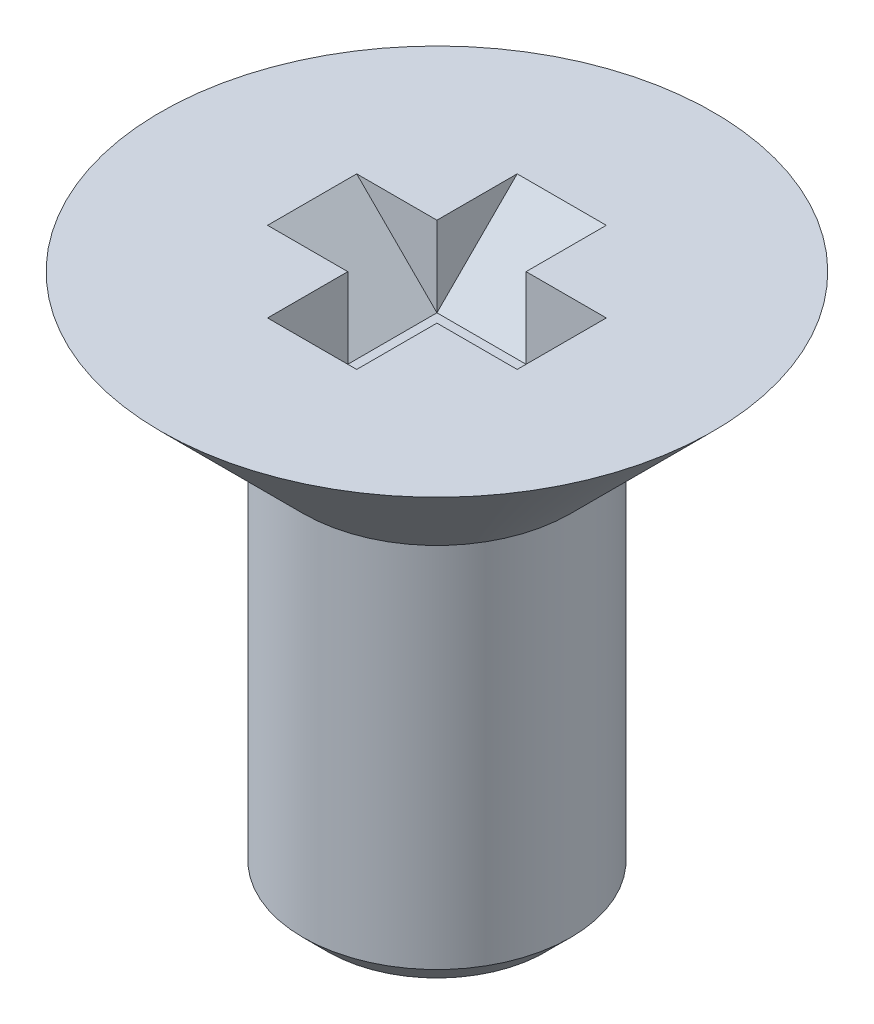
SolidWorks part; units mm, degrees
material "Сталь"
ref_plane "Спереди" through (0, 0, 0) normal (0, 0, 1) x (1, 0, 0)
ref_plane "Сверху" through (0, 0, 0) normal (0, 1, 0) x (1, 0, 0)
ref_plane "Справа" through (0, 0, 0) normal (1, 0, 0) x (0, 0, -1)
sketch "Эскиз1" plane through (0, 0, 0) normal (0, 0, 1) x (1, 0, 0)
  line L0 (0, 0) -> (3.1, 0)
  line L1 (3.1, 0) -> (1.5, -1.6)
  line L2 (1.5, -1.6) -> (1.5, -6)
  line L3 (0, 0) -> (0, -5.6071) construction
  line L4 (1.5, -6) -> (0, -6)
  line L5 (0, -6) -> (0, 0)
  dimension "D1" = 45
  dimension "D2" = 1.6
  dimension "D3" = 1.5
  dimension "D4" = 6
revolve "Повернуть1" add sketch "Эскиз1" angle 360 about L3
cosmetic thread "Условное изображение резьбы1" parameters "D1"=4.3, "D2"=2.439
chamfer "Фаска1" distance 0.2805 angle 45 1 edges at (0, -6, 1.5)
sketch "Эскиз2" plane through (0, 0, 0) normal (0, 0, 1) x (1, 0, 0)
  line L0 (0, 0) -> (0, -1.4)
  line L1 (0, -1.4) -> (-1.4, 0)
  line L2 (3.1, 0) -> (-3.1, 0) construction
  line L3 (-1.4, 0) -> (0, 0)
  dimension "D1" = 45
  dimension "D2" = 1.4
extrude "Вырез-Вытянуть1" cut sketch "Эскиз2" along normal blind 0.5 and the other way blind 0.5
pattern_circular "Круговой массив1" count 4 over 360 about axis through (0, -1.6, 0) along (0, -1, 0) of "Вырез-Вытянуть1"
ref_plane "Плоскость1" through (0, -0.9, 0) normal (0, 1, 0) x (1, 0, 0)
sketch "Эскиз3" plane through (0, -0.9, 0) normal (0, 1, 0) x (1, 0, 0)
  line L0 (-0.5, 0.5) -> (-0.5, -0.5)
  line L1 (-0.5, -0.5) -> (0.5, -0.5)
  line L2 (0.5, -0.5) -> (0.5, 0.5)
  line L3 (0.5, 0.5) -> (-0.5, 0.5)
extrude "Бобышка-Вытянуть1" add sketch "Эскиз3" against normal blind 2
